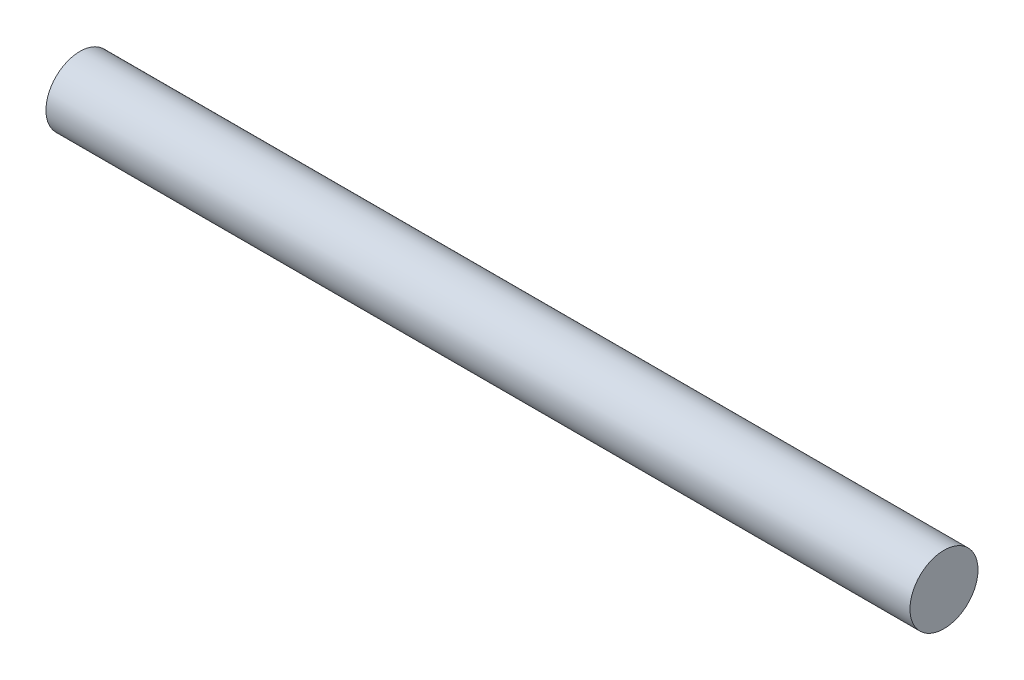
SolidWorks part; units mm, degrees
material "Brass"
ref_plane "Front Plane" through (0, 0, 0) normal (0, 0, 1) x (1, 0, 0)
ref_plane "Top Plane" through (0, 0, 0) normal (0, 1, 0) x (1, 0, 0)
ref_plane "Right Plane" through (0, 0, 0) normal (1, 0, 0) x (0, 0, -1)
sketch "Sketch1" plane through (0, 0, 0) normal (1, 0, 0) x (0, 0, -1)
  circle A0 centre (0, 0) radius 2.5
  dimension "D1" = 5
extrude "Base" add sketch "Sketch1" along normal blind 63.5
